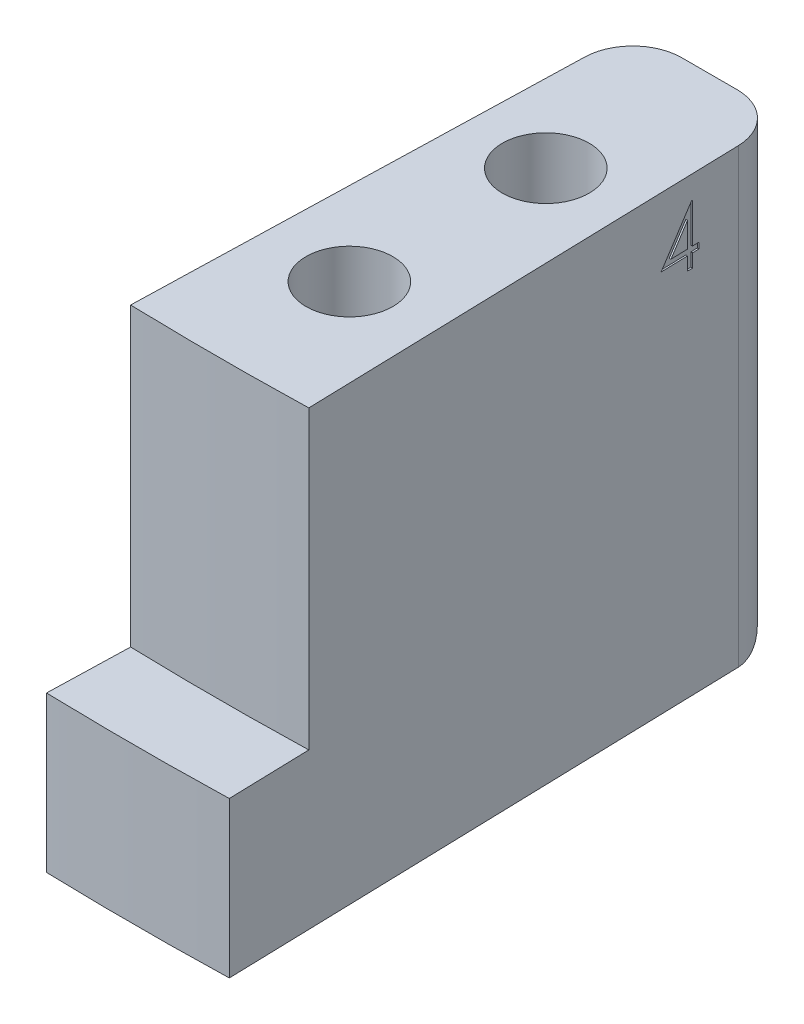
SolidWorks part; units mm, degrees
ref_plane "前视基准面" through (0, 0, 0) normal (0, 0, 1) x (1, 0, 0)
ref_plane "上视基准面" through (0, 0, 0) normal (0, 1, 0) x (1, 0, 0)
ref_plane "右视基准面" through (0, 0, 0) normal (1, 0, 0) x (0, 0, -1)
ref_axis "顶盖中心轴" through (0, -55, 0) along (0, 1, 0)
sketch "草图1" plane through (0, 0, 0) normal (0, 1, 0) x (1, 0, 0)
  line L0 (-4.7487, -170.0072) -> (-4.8586, -173.9402) construction
  line L1 (0, 0) -> (0, -125.794) construction
  line L3 (-4.6089, -165) -> (4.6089, -165)
  line L4 (-4.6089, -165) -> (-5.5843, -199.922)
  line L5 (4.6089, -165) -> (5.5843, -199.922)
  arc A0 (-5.4447, -194.924) -> (5.4447, -194.924) centre (0, 0) ccw
  arc A1 (-5.5843, -199.922) -> (5.5843, -199.922) centre (0, 0) ccw
  dimension "D1" = 1.6
  dimension "D2" = 195
  dimension "D4" = 200
  dimension "D3" = 165
extrude "主体" add sketch "草图1" along normal blind 27.6 contours L4 A0 L5 L3 region at (0, 0, 180.4033)
extrude "插销" add sketch "草图1<3>" along normal blind 9.5 contours L4 A1 L5 A0 region at (0, 0, 197.4849)
sketch "草图1<3>" plane through (0, 0, 0) normal (0, 1, 0) x (1, 0, 0) same geometry as "草图1"
ref_plane "对称面" through (0, 0, 0) normal (1, 0, 0) x (0, 0, -1)
fillet "圆角1" radius 3 3 edges at (-4.6089, 13.8, 165) (4.6089, 13.8, 165) (0, 0, 165)
hole_wizard "M5 间隙孔1" positions "草图4" profile "草图5" hole size "M5" standard "ISO" end condition up to next
sketch "草图4" plane through (0, 27.6, 0) normal (0, 1, 0) x (1, 0, 0)
  line L0 (0, -13.75) -> (0, 13.75) construction
  point P0 (0, -187)
  point P2 (0, -175)
  dimension "D1" = 175
  dimension "D2" = 187
sketch "草图5" plane through (0, 27.6, 187) normal (1, 0, 0) x (0, 0, 1)
  line L0 (0, 0) -> (0, 27.6)
  line L1 (0, 27.6) -> (2.65, 27.6)
  line L2 (2.65, 27.6) -> (2.65, 0)
  line L5 (2.65, 0) -> (0, 0)
  line L11 (0, -6.35) -> (0, 107.95) construction
  dimension "通孔孔直径" = 5.3
  dimension "通孔孔深度" = 27.6
sketch "草图6" plane through (0, 0, 0) normal (0, -1, 0) x (1, 0, 0)
  line L1 (0, 179.792) -> (-4.15, 177.396)
  line L2 (-4.15, 177.396) -> (-4.15, 172.604)
  line L3 (-4.15, 172.604) -> (0, 170.208)
  line L4 (0, 170.208) -> (4.15, 172.604)
  line L5 (4.15, 172.604) -> (4.15, 177.396)
  line L6 (4.15, 177.396) -> (0, 179.792)
  line L7 (0, 191.792) -> (-4.15, 189.396)
  line L8 (-4.15, 189.396) -> (-4.15, 184.604)
  line L9 (-4.15, 184.604) -> (0, 182.208)
  line L10 (0, 182.208) -> (4.15, 184.604)
  line L11 (4.15, 184.604) -> (4.15, 189.396)
  line L12 (4.15, 189.396) -> (0, 191.792)
  circle A0 centre (0, 175) radius 4.15 construction
  circle A1 centre (0, 187) radius 4.15 construction
  point P9 (0, 182.208)
  point P17 (0, 170.208)
  dimension "D1" = 8.3
  dimension "D2" = 8.3
extrude "切除-拉伸1" cut sketch "草图6" against normal blind 5
sketch "草图7" plane through (0, 0, 0) normal (0.9996, 0, -0.0279) x (-0.0279, 0, -0.9996)
  line L0 (-167.9817, 0.0012) -> (-167.9817, 27.6) construction
  line L2 (-167.9817, 27.6) -> (-195, 27.6) construction
  text T0 "4"
  point P1 (0, 0)
  point P4 (0, 0)
  point P6 (-170.6934, 29.6)
  dimension "D1" = 5
  dimension "D2" = 5
extrude "切除-拉伸2" cut sketch "草图7" against normal blind 0.1
